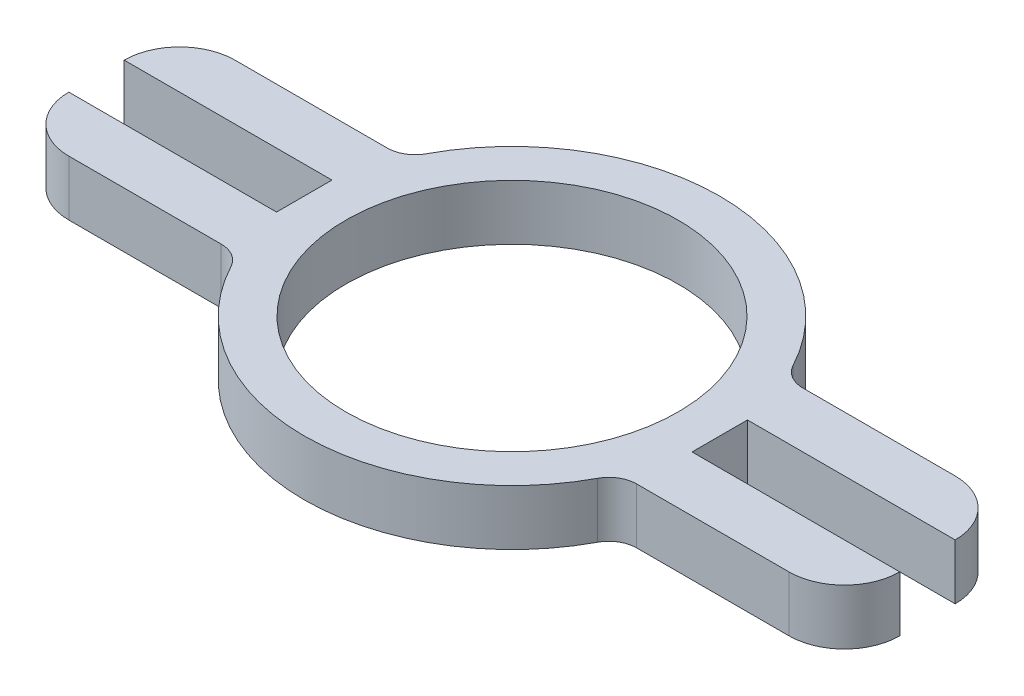
SolidWorks part; units mm, degrees
material "PTFE (general)"
ref_plane "Front Plane" through (0, 0, 0) normal (0, 0, 1) x (1, 0, 0)
ref_plane "Top Plane" through (0, 0, 0) normal (0, 1, 0) x (1, 0, 0)
ref_plane "Right Plane" through (0, 0, 0) normal (1, 0, 0) x (0, 0, -1)
sketch "Sketch1" plane through (0, 0, 0) normal (0, 1, 0) x (1, 0, 0)
  line L10 (68.7386, 30) -> (150, 30)
  line L11 (150, 30) -> (150, -30)
  line L12 (150, -30) -> (68.7386, -30)
  line L14 (0, 75) -> (0, -75)
  arc A2 (68.7386, 30) -> (0, 75) centre (0, 0) ccw
  arc A3 (0, -75) -> (68.7386, -30) centre (0, 0) ccw
  dimension "D1" = 150
  dimension "D3" = 60
extrude "Boss-Extrude1" add sketch "Sketch1" along normal blind 20
sketch "Sketch2" plane through (0, 20, 0) normal (0, 1, 0) x (1, 0, 0)
  line L0 (0, 60) -> (0, -60)
  line L1 (75, 10) -> (150, 10)
  line L2 (150, 10) -> (150, -10)
  line L3 (150, -10) -> (75, -10)
  line L4 (75, -10) -> (75, 10)
  line L8 (150, -30) -> (150, 30) construction
  arc A0 (0, -60) -> (0, 60) centre (0, 0) ccw
  point P6 (75, 0)
  dimension "D1" = 120
  dimension "D2" = 75
  dimension "D3" = 20
extrude "Cut-Extrude1" cut sketch "Sketch2" against normal up to surface (20 mm away) up to face at (75.1495, 0, 0)
mirror "Mirror1" about plane through (0, 0, 0) normal (1, 0, 0) of "Boss-Extrude1", "Cut-Extrude1"
fillet "Fillet1" radius 10 4 edges at (-68.7386, 10, 30) (68.7386, 10, 30) (68.7386, 10, -30) (-68.7386, 10, -30)
fillet "Fillet2" radius 20 4 edges at (-150, 10, 30) (-150, 10, -30) (150, 10, -30) (150, 10, 30)
ref_axis "Axis1" through (0, -22.2105, 0) along (0, 1, 0)
